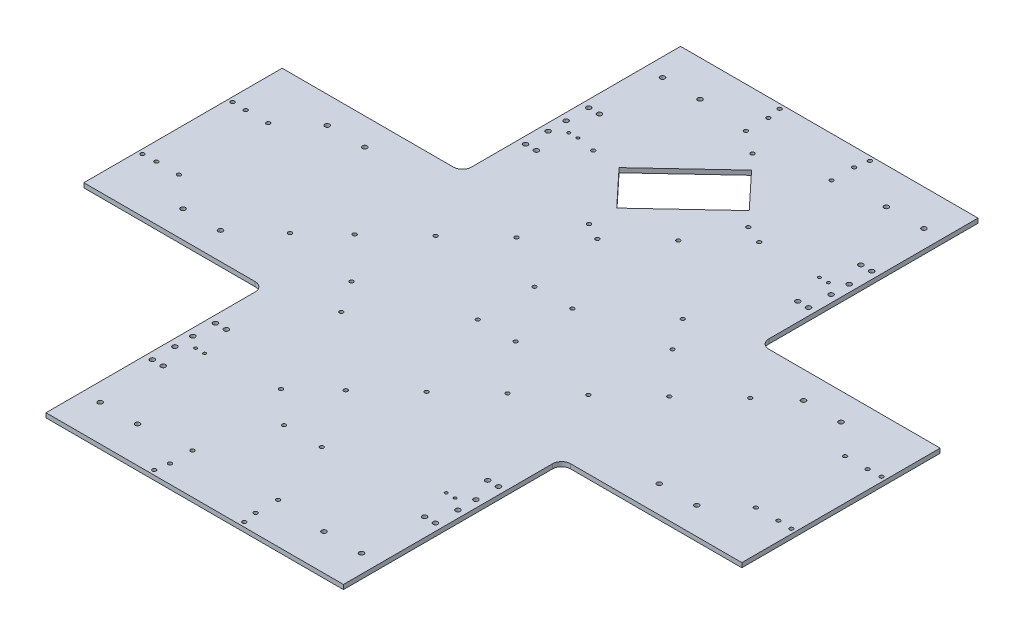
SolidWorks part; units mm, degrees
other "Markup1"
sketch "Sketch8"
material "3.0205 (EN-AW 1200)"
ref_plane "前视基准面" through (0, 0, 0) normal (0, 0, 1) x (1, 0, 0)
ref_plane "上视基准面" through (0, 0, 0) normal (0, 1, 0) x (1, 0, 0)
ref_plane "右视基准面" through (0, 0, 0) normal (1, 0, 0) x (0, 0, -1)
other "Configuration Table"
sketch "Sketch1" plane through (0, 0, 0) normal (0, 1, 0) x (1, 0, 0)
  line L0 (165, 352) -> (-165, 352)
  line L1 (-165, 352) -> (-165, 110)
  line L2 (-165, 110) -> (-365, 110)
  line L5 (-365, 110) -> (-365, -110)
  line L6 (0, 352) -> (0, -66.8675) construction
  line L7 (-365, 0) -> (131.0517, 0) construction
  line L8 (365, 110) -> (365, -110)
  line L11 (165, 110) -> (365, 110)
  line L12 (165, 352) -> (165, 110)
  line L13 (165, -352) -> (165, -110)
  line L14 (165, -110) -> (365, -110)
  line L19 (-165, -110) -> (-365, -110)
  line L20 (-165, -352) -> (-165, -110)
  line L21 (165, -352) -> (-165, -352)
  point P21 (365, 0)
  dimension "D1" = 165
  dimension "D2" = 200
  dimension "D3" = 110
  dimension "D4" = 242
extrude "Boss-Extrude1" add sketch "Sketch1" along normal blind 5
sketch "Sketch2" plane through (0, 5, 0) normal (0, 1, 0) x (1, 0, 0)
  line L3 (365, -110) -> (365, 110) construction
  line L4 (-56.7455, 0) -> (47.5165, 0) construction
  line L5 (0, 54.7142) -> (0, -64.2255) construction
  line L7 (165, 352) -> (-165, 352) construction
  circle A0 centre (345, 49.5) radius 2.125
  circle A1 centre (320, 49.5) radius 2.125
  circle A7 centre (320, -49.5) radius 2.125
  circle A8 centre (345, -49.5) radius 2.125
  circle A9 centre (-345, -49.5) radius 2.125
  circle A10 centre (-320, -49.5) radius 2.125
  circle A13 centre (-320, 49.5) radius 2.125
  circle A14 centre (-345, 49.5) radius 2.125
  circle A15 centre (47.5, 332) radius 2.125
  circle A16 centre (47.5, 307) radius 2.125
  circle A17 centre (-47.5, 307) radius 2.125
  circle A18 centre (-47.5, 332) radius 2.125
  circle A19 centre (-47.5, -332) radius 2.125
  circle A20 centre (-47.5, -307) radius 2.125
  circle A21 centre (47.5, -307) radius 2.125
  circle A22 centre (47.5, -332) radius 2.125
  dimension "D3" = 49.5
  dimension "D5" = 4.25
  dimension "D7" = 4.25
  dimension "D9" = 4.25
  dimension "D10" = 4.25
  dimension "D2" = 47.5
  dimension "D4" = 25
  dimension "D6" = 20
  dimension "20" = 20
  dimension "D13" = 25
extrude "Cut-Extrude1" cut sketch "Sketch2" against normal blind 3
sketch "Sketch4" plane through (0, 5, 0) normal (0, 1, 0) x (1, 0, 0)
  line L0 (-165, 352) -> (-165, 110) construction
  line L1 (165, 352) -> (-165, 352) construction
  line L2 (0, 46.9886) -> (0, -40.2904) construction
  line L3 (-35.103, 0) -> (92.4951, 0) construction
  line L5 (165, -352) -> (165, -110) construction
  circle A0 centre (-157, 172) radius 2.6
  circle A1 centre (-145, 172) radius 2.6
  circle A2 centre (-157, 197) radius 2.6
  circle A3 centre (-157, 217) radius 2.6
  circle A4 centre (-157, 242) radius 2.6
  circle A5 centre (-145, 242) radius 2.6
  circle A6 centre (145, 242) radius 2.6
  circle A7 centre (157, 242) radius 2.6
  circle A8 centre (157, 217) radius 2.6
  circle A9 centre (157, 197) radius 2.6
  circle A10 centre (145, 172) radius 2.6
  circle A11 centre (157, 172) radius 2.6
  circle A12 centre (157, -172) radius 2.6
  circle A13 centre (145, -172) radius 2.6
  circle A14 centre (157, -197) radius 2.6
  circle A15 centre (157, -217) radius 2.6
  circle A16 centre (157, -242) radius 2.6
  circle A17 centre (145, -242) radius 2.6
  circle A18 centre (-145, -242) radius 2.6
  circle A19 centre (-157, -242) radius 2.6
  circle A20 centre (-157, -217) radius 2.6
  circle A21 centre (-157, -197) radius 2.6
  circle A22 centre (-145, -172) radius 2.6
  circle A23 centre (-157, -172) radius 2.6
  circle A24 centre (144, -207) radius 1.6
  circle A25 centre (-144, -207) radius 1.6
  circle A26 centre (144, 207) radius 1.6
  circle A27 centre (-144, 207) radius 1.6
  circle A28 centre (134, -207) radius 1.6
  circle A29 centre (-134, -207) radius 1.6
  circle A30 centre (134, 207) radius 1.6
  circle A31 centre (-134, 207) radius 1.6
  dimension "D3" = 5.2
  dimension "D4" = 5.2
  dimension "D5" = 8
  dimension "D6" = 8
  dimension "D9" = 5.2
  dimension "D10" = 5.2
  dimension "D11" = 5.2
  dimension "D12" = 5.2
  dimension "D19" = 3.2
  dimension "D20" = 21
  dimension "D21" = 10
  dimension "D22" = 3.2
  dimension "D23" = 10
  dimension "D1" = 8
  dimension "D2" = 20
  dimension "D7" = 8
  dimension "D8" = 20
  dimension "D13" = 25
  dimension "D14" = 20
  dimension "D15" = 25
  dimension "D16" = 25
  dimension "D17" = 110
  dimension "D18" = 0
extrude "Cut-Extrude3" cut sketch "Sketch4" against normal blind 10
sketch "Sketch5" plane through (0, 5, 0) normal (0, 1, 0) x (1, 0, 0)
  line L0 (165, 352) -> (-165, 352) construction
  line L5 (-46.9195, 0) -> (66.6223, 0) construction
  line L6 (0, 59.0569) -> (0, -54.4849) construction
  line L10 (-365, 110) -> (-365, -110) construction
  circle A0 centre (-50, 347) radius 2.125
  circle A1 centre (50, 347) radius 2.125
  circle A2 centre (50, -347) radius 2.125
  circle A3 centre (-50, -347) radius 2.125
  circle A4 centre (-360, 50) radius 2.125
  circle A5 centre (-360, -50) radius 2.125
  circle A6 centre (360, -50) radius 2.125
  circle A7 centre (360, 50) radius 2.125
  dimension "D1" = 4.25
  dimension "D2" = 4.25
  dimension "D3" = 50
  dimension "D6" = 4.25
  dimension "D7" = 4.25
  dimension "5" = 5
  dimension "D4" = 50
  dimension "D5" = 50
  dimension "D8" = 50
  dimension "D9" = 5
  dimension "D10" = 5
extrude "Cut-Extrude4" cut sketch "Sketch5" against normal blind 10
fillet "Fillet1" radius 10 4 edges at (-165, 2.5, -110) (-165, 2.5, 110) (165, 2.5, 110) (165, 2.5, -110)
sketch "Sketch6" plane through (0, 5, 0) normal (0, 1, 0) x (1, 0, 0)
  line L0 (165, 352) -> (-165, 352) construction
  line L1 (-165, 352) -> (-165, 120) construction
  line L3 (0, 50.3702) -> (0, -42.7646) construction
  line L4 (-54.8568, 0) -> (91.2004, 0) construction
  line L5 (365, 110) -> (175, 110) construction
  line L6 (365, -110) -> (365, 110) construction
  circle A0 centre (-145, 312) radius 2.6
  circle A1 centre (-103.4, 312) radius 2.6
  circle A4 centre (103.4, 312) radius 2.6
  circle A5 centre (145, 312) radius 2.6
  circle A6 centre (145, -312) radius 2.6
  circle A7 centre (103.4, -312) radius 2.6
  circle A8 centre (-103.4, -312) radius 2.6
  circle A9 centre (-145, -312) radius 2.6
  circle A10 centre (243.4, 80) radius 2.6
  circle A11 centre (285, 80) radius 2.6
  circle A12 centre (285, -80) radius 2.6
  circle A13 centre (243.4, -80) radius 2.6
  circle A14 centre (-243.4, -80) radius 2.6
  circle A15 centre (-285, -80) radius 2.6
  circle A16 centre (-285, 80) radius 2.6
  circle A17 centre (-243.4, 80) radius 2.6
  dimension "D1" = 5.2
  dimension "D2" = 5.2
  dimension "D3" = 5.2
  dimension "D4" = 5.2
  dimension "D5" = 40
  dimension "D8" = 30
  dimension "D6" = 20
  dimension "D7" = 41.6
  dimension "D9" = 80
  dimension "D10" = 41.6
extrude "Cut-Extrude5" cut sketch "Sketch6" against normal blind 10
sketch "Sketch7" plane through (0, 5, 0) normal (0, 1, 0) x (1, 0, 0)
  line L0 (164.5832, 153.9982) -> (-155.4181, -145.4226) construction
  line L1 (165, 299.5544) -> (-272.7048, -110) construction
  line L2 (165, 120) -> (165, 352) construction
  line L3 (-365, -110) -> (-175, -110) construction
  line L4 (272.7048, 110) -> (-165, -299.5544) construction
  line L5 (365, 110) -> (175, 110) construction
  line L6 (-165, -120) -> (-165, -352) construction
  line L7 (-268.9942, -53.3124) -> (-51.1439, -286.1364) construction
  line L8 (84.7791, 253.9237) -> (328.5288, -6.5799) construction
  line L9 (-72.423, 77.401) -> (72.423, -77.401) construction
  line L11 (-380.0049, -355.5654) -> (380.0049, -355.5654) construction
  line L12 (-380.0049, -355.5654) -> (-380.0049, 355.5654) construction
  line L13 (-380.0049, 355.5654) -> (380.0049, 355.5654) construction
  line L14 (380.0049, -355.5654) -> (380.0049, 355.5654) construction
  line L15 (-380.0049, -355.5654) -> (380.0049, 355.5654) construction
  line L16 (-380.0049, 355.5654) -> (380.0049, -355.5654) construction
  circle A4 centre (-72.423, 77.401) radius 2.125
  circle A5 centre (-26.0555, 120.7864) radius 2.125
  circle A6 centre (20.3121, 164.1719) radius 2.125
  circle A7 centre (66.6796, 207.5574) radius 2.125
  circle A8 centre (-118.7906, 34.0155) radius 2.125
  circle A9 centre (-165.1581, -9.37) radius 2.125
  circle A10 centre (-202.2522, -44.0784) radius 2.125
  circle A11 centre (-57.4061, -198.8803) radius 2.125
  circle A12 centre (-20.3121, -164.1719) radius 2.125
  circle A13 centre (26.0555, -120.7864) radius 2.125
  circle A14 centre (211.5257, 52.7555) radius 2.125
  circle A15 centre (165.1581, 9.37) radius 2.125
  circle A16 centre (118.7906, -34.0155) radius 2.125
  circle A17 centre (72.423, -77.401) radius 2.125
  point P53 (0, 0)
  dimension "D6" = 4.25
  dimension "D7" = 4.25
  dimension "D8" = 4.25
  dimension "D9" = 4.25
  dimension "D10" = 4.25
  dimension "D11" = 4.25
  dimension "D12" = 4.25
  dimension "D1" = 106
  dimension "D3" = 20
  dimension "D4" = 20
  dimension "D5" = 0
  dimension "D13" = 63.5
  dimension "D14" = 63.5
  dimension "D15" = 50.8
  dimension "D16" = 63.5
  dimension "D17" = 63.5
  dimension "D18" = 63.5
extrude "Cut-Extrude6" cut sketch "Sketch7" against normal blind 10
sketch "Sketch9" plane through (0, 5, 0) normal (0, 1, 0) x (1, 0, 0)
  line L0 (167.9289, 112.9289) -> (-167.9289, -112.9289) construction
  line L1 (80.349, 117.7232) -> (149.9169, 14.2734) construction
  line L2 (-142.2885, -25.6171) -> (-87.1446, -107.6179) construction
  line L3 (0, 45.0584) -> (0, -52.9183) construction
  line L4 (-44.6513, 0) -> (48.0404, 0) construction
  line L5 (165, 352) -> (-165, 352) construction
  arc A0 (165, 120) -> (175, 110) centre (175, 120) ccw construction
  arc A1 (-165, -120) -> (-175, -110) centre (-175, -120) ccw construction
  circle A2 centre (-121.5605, -56.4403) radius 2.1
  circle A3 centre (-98.123, -91.2926) radius 2.1
  circle A4 centre (98.123, 91.2926) radius 2.1
  circle A5 centre (121.5605, 56.4403) radius 2.1
  circle A7 centre (21, 232) radius 2.1
  circle A8 centre (-21, 232) radius 2.1
  circle A9 centre (-21, -232) radius 2.1
  circle A10 centre (21, -232) radius 2.1
  dimension "D3" = 4.2
  dimension "D4" = 4.2
  dimension "D5" = 4.2
  dimension "D6" = 4.2
  dimension "D11" = 120
  dimension "D12" = 4.2
  dimension "D1" = 70
  dimension "D2" = 70
  dimension "D7" = 21
  dimension "D8" = 21
  dimension "D9" = 21
  dimension "D10" = 21
  dimension "D13" = 21
extrude "Cut-Extrude7" cut sketch "Sketch9" against normal blind 10
sketch "Sketch10" plane through (0, 5, 0) normal (0, 1, 0) x (1, 0, 0)
  line L0 (70.1652, 238.2086) -> (-130.5354, 50.4158) construction
  line L5 (-6.3046, 303.6061) -> (-217.4253, 106.0633) construction
  line L6 (66.6796, 207.5574) -> (-72.423, 77.401) construction
  line L7 (46.2747, 215.8546) -> (-22.0489, 288.8744) construction
  line L8 (-45, 130.4501) -> (-113.3236, 203.4699) construction
  line L9 (165, 120) -> (165, 352) construction
  line L10 (-114.9608, 133.4634) -> (31.7887, 270.7749) construction
  line L11 (-6.6761, 272.4449) -> (30.9019, 232.2841)
  line L12 (30.9019, 232.2841) -> (-45.0387, 161.2275)
  line L13 (-45.0387, 161.2275) -> (-82.6166, 201.3884)
  line L14 (-82.6166, 201.3884) -> (-6.6761, 272.4449)
  circle A0 centre (46.2747, 215.8546) radius 2.125
  circle A1 centre (-45, 130.4501) radius 2.125
  circle A3 centre (-113.3236, 203.4699) radius 2.125
  circle A4 centre (-22.0489, 288.8744) radius 2.125
  dimension "D3" = 4.25
  dimension "D4" = 4.25
  dimension "D7" = 4.25
  dimension "D8" = 4.25
  dimension "D1" = 20
  dimension "D2" = 100
  dimension "D5" = 210
  dimension "D6" = 125
  dimension "D9" = 50
  dimension "D10" = 55
  dimension "D11" = 27.5
  dimension "D12" = 104
extrude "Cut-Extrude8" cut sketch "Sketch10" against normal blind 10
sketch "Sketch11" plane through (0, 5, 0) normal (0, 1, 0) x (1, 0, 0)
  line L1 (-365, 110) -> (-365, -110) construction
  line L2 (-175, 110) -> (-365, 110) construction
  circle A4 centre (-15, 40) radius 2.125
  circle A5 centre (27, 40) radius 2.125
  circle A6 centre (-15, -23) radius 2.125
  circle A7 centre (27, -23) radius 2.125
  dimension "D3" = 4.25
  dimension "D4" = 4.25
  dimension "D5" = 4.25
  dimension "D6" = 4.25
  dimension "D1" = 63
  dimension "D2" = 42
  dimension "D7" = 350
  dimension "D8" = 70
extrude "Cut-Extrude9" cut sketch "Sketch11" against normal blind 10
